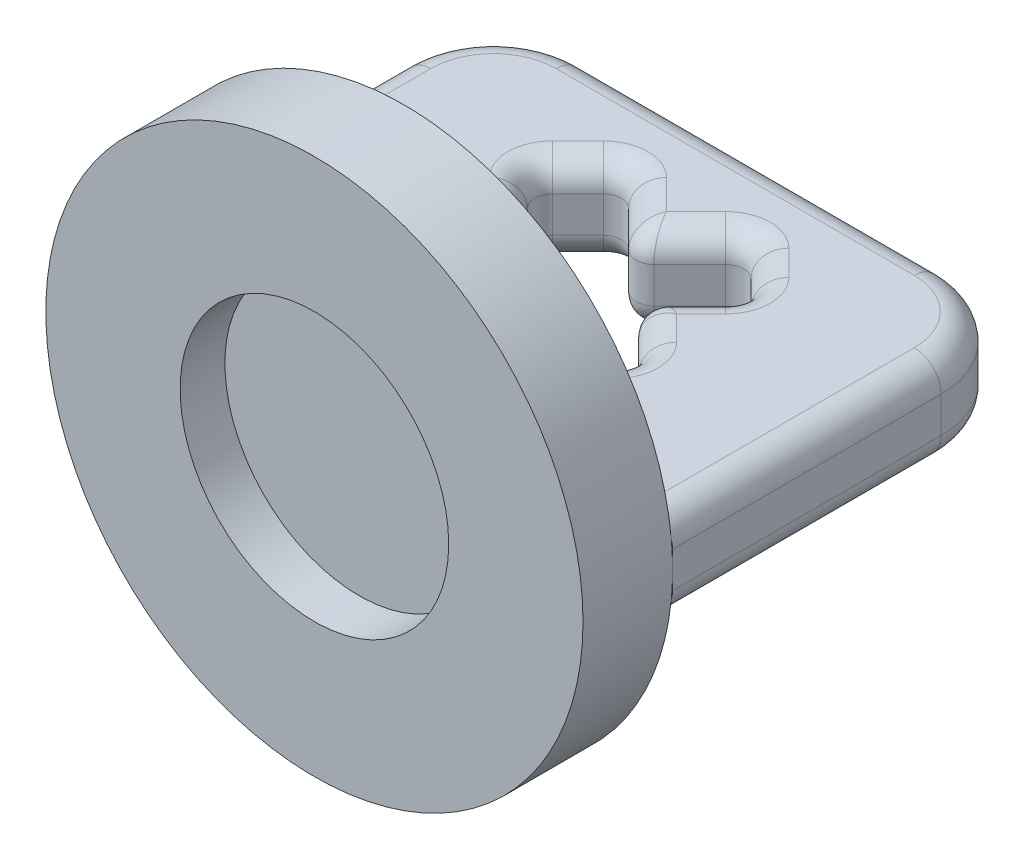
SolidWorks part; units mm, degrees
ref_plane "Alzado" through (0, 0, 0) normal (0, 0, 1) x (1, 0, 0)
ref_plane "Planta" through (0, 0, 0) normal (0, 1, 0) x (1, 0, 0)
ref_plane "Vista lateral" through (0, 0, 0) normal (1, 0, 0) x (0, 0, -1)
sketch "Croquis1" plane through (0, 0, 0) normal (0, 0, 1) x (1, 0, 0)
  circle A0 centre (0, 0) radius 30
  dimension "D1" = 60
extrude "Saliente-Extruir1" add sketch "Croquis1" along normal blind 10
sketch "Croquis2" plane through (0, 0, 0) normal (0, 1, 0) x (1, 0, 0)
  line L0 (30, -10) -> (30, 0) construction
  line L1 (-30, 0) -> (30, 0)
  line L2 (-30, 0) -> (-30, 40)
  line L3 (-30, 40) -> (30, 40)
  line L4 (30, 0) -> (30, 40)
  dimension "D1" = 40
extrude "Saliente-Extruir2" add sketch "Croquis2" along normal mid plane 10
fillet "Redondeo1" radius 10 2 edges at (30, 0, -40) (-30, 0, -40)
fillet "Redondeo2" radius 3 10 edges at (30, -5, -15) (27.0711, -5, -37.0711) (-30, -5, -15) (-27.0711, -5, -37.0711) (30, 5, -15) (27.0711, 5, -37.0711) (-30, 5, -15) (-27.0711, 5, -37.0711) (0, -5, -40) (0, 5, -40)
sketch "Croquis3" plane through (0, 0, 10) normal (0, 0, 1) x (1, 0, 0)
  circle A0 centre (0, 0) radius 15
  dimension "D1" = 30
extrude "Cortar-Extruir1" cut sketch "Croquis3" against normal blind 5
sketch "Croquis5" plane through (0, 5, 0) normal (0, 1, 0) x (1, 0, 0)
  line L0 (-11.0751, 27.6816) -> (-8.2466, 30.51)
  line L1 (-5.4182, 30.51) -> (-1.4142, 26.5061)
  line L2 (1.4142, 26.5061) -> (5.4182, 30.51)
  line L3 (8.2466, 30.51) -> (11.0751, 27.6816)
  line L4 (11.0751, 24.8532) -> (7.6361, 21.4142)
  line L5 (7.6361, 18.5858) -> (11.0751, 15.1468)
  line L6 (11.0751, 12.3184) -> (8.2466, 9.49)
  line L7 (5.4182, 9.49) -> (1.4142, 13.4939)
  line L8 (-1.4142, 13.4939) -> (-5.4182, 9.49)
  line L9 (-8.2466, 9.49) -> (-11.0751, 12.3184)
  line L10 (-11.0751, 15.1468) -> (-7.6361, 18.5858)
  line L11 (-7.6361, 21.4142) -> (-11.0751, 24.8532)
  line L12 (0, 0) -> (0, 40) construction
  line L13 (-20, 40) -> (20, 40) construction
  line L14 (30, 20) -> (-30, 20) construction
  line L15 (-30, 0) -> (-30, 30) construction
  arc A0 (7.6361, 21.4142) -> (7.6361, 18.5858) centre (9.0503, 20) ccw
  arc A1 (11.0751, 15.1468) -> (11.0751, 12.3184) centre (9.6608, 13.7326) cw
  arc A2 (8.2466, 9.49) -> (5.4182, 9.49) centre (6.8324, 10.9042) cw
  arc A3 (1.4142, 13.4939) -> (-1.4142, 13.4939) centre (0, 12.0797) ccw
  arc A4 (-5.4182, 9.49) -> (-8.2466, 9.49) centre (-6.8324, 10.9042) cw
  arc A5 (-11.0751, 12.3184) -> (-11.0751, 15.1468) centre (-9.6608, 13.7326) cw
  arc A6 (-7.6361, 18.5858) -> (-7.6361, 21.4142) centre (-9.0503, 20) ccw
  arc A7 (-1.4142, 26.5061) -> (1.4142, 26.5061) centre (0, 27.9203) ccw
  arc A8 (11.0751, 27.6816) -> (11.0751, 24.8532) centre (9.6608, 26.2674) cw
  arc A9 (5.4182, 30.51) -> (8.2466, 30.51) centre (6.8324, 29.0958) cw
  arc A10 (-8.2466, 30.51) -> (-5.4182, 30.51) centre (-6.8324, 29.0958) cw
  arc A11 (-11.0751, 27.6816) -> (-11.0751, 24.8532) centre (-9.6608, 26.2674) ccw
  point P7 (6.2219, 20)
  point P18 (0, 20)
  point P21 (6.2219, 20)
  point P24 (12.4893, 13.7326)
  point P27 (6.8324, 8.0757)
  point P34 (0, 14.9082)
  point P37 (-6.8324, 8.0757)
  point P40 (-12.4893, 13.7326)
  point P43 (-6.2219, 20)
  point P46 (0, 25.0918)
  point P49 (12.4893, 26.2674)
  point P52 (6.8324, 31.9243)
  point P55 (-6.8324, 31.9243)
  point P58 (-12.4893, 26.2674)
  dimension "D2" = 2
  dimension "D1" = 8
extrude "Cortar-Extruir3" cut sketch "Croquis5" against normal through all
fillet "Redondeo4" radius 3 48 edges at (6.8324, 5, -31.0958) (9.6608, 5, -29.0958) (11.6608, 5, -26.2674) (9.3556, 5, -23.1337) (7.0503, 5, -20) (9.3556, 5, -16.8663) (11.6608, 5, -13.7326) (9.6608, 5, -10.9042) (6.8324, 5, -8.9042) (3.4162, 5, -11.4919) (0, 5, -14.0797) (-3.4162, 5, -11.4919) (-6.8324, 5, -8.9042) (-9.6608, 5, -10.9042) (-11.6608, 5, -13.7326) (-9.3556, 5, -16.8663) (-7.0503, 5, -20) (-9.3556, 5, -23.1337) (-11.6608, 5, -26.2674) (-9.6608, 5, -29.0958) (-6.8324, 5, -31.0958) (-3.4162, 5, -28.5081) (0, 5, -25.9203) (0, -5, -25.9203) (-3.4162, -5, -28.5081) (-6.8324, -5, -31.0958) (-9.6608, -5, -29.0958) (-11.6608, -5, -26.2674) (-9.3556, -5, -23.1337) (-7.0503, -5, -20) (-9.3556, -5, -16.8663) (-11.6608, -5, -13.7326) (-9.6608, -5, -10.9042) (-6.8324, -5, -8.9042) (-3.4162, -5, -11.4919) (0, -5, -14.0797) (3.4162, -5, -11.4919) (6.8324, -5, -8.9042) (9.6608, -5, -10.9042) (11.6608, -5, -13.7326) (9.3556, -5, -16.8663) (7.0503, -5, -20) (9.3556, -5, -23.1337) (11.6608, -5, -26.2674) (9.6608, -5, -29.0958) (6.8324, -5, -31.0958) (3.4162, 5, -28.5081) (3.4162, -5, -28.5081)
